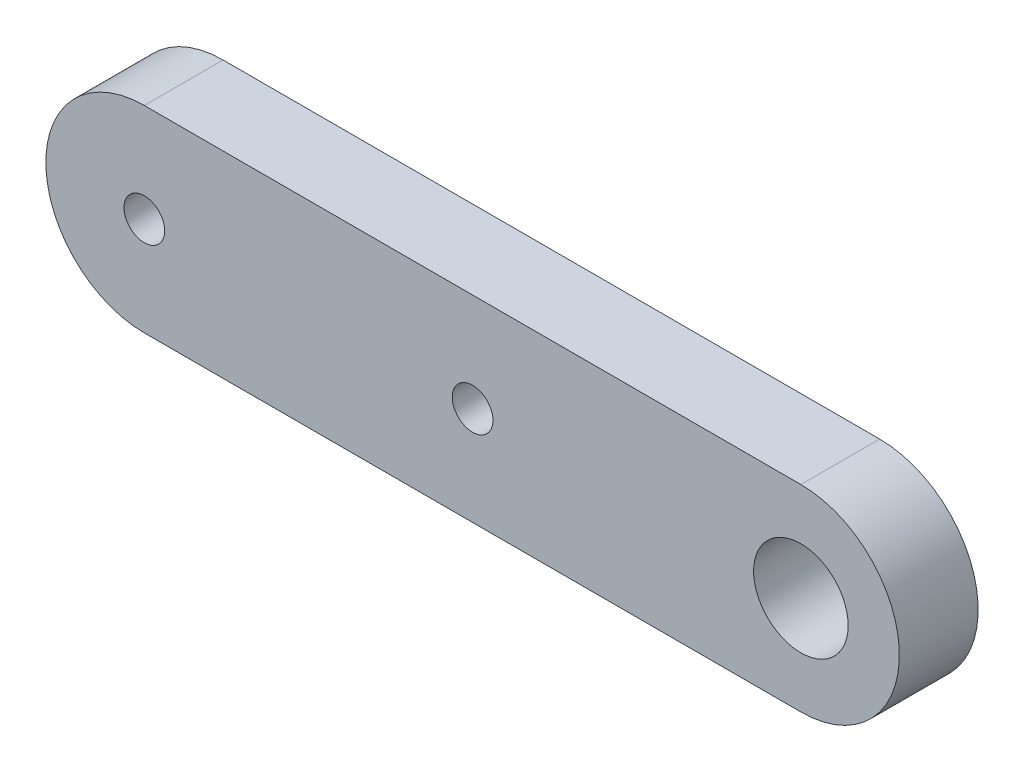
SolidWorks part; units mm, degrees
material "Pine"
ref_plane "Front Plane" through (0, 0, 0) normal (0, 0, 1) x (1, 0, 0)
ref_plane "Top Plane" through (0, 0, 0) normal (0, 1, 0) x (1, 0, 0)
ref_plane "Right Plane" through (0, 0, 0) normal (1, 0, 0) x (0, 0, -1)
sketch "Sketch1" plane through (0, 0, 0) normal (0, 0, 1) x (1, 0, 0)
  line L0 (0, 7.5) -> (50, 7.5)
  line L1 (50, -7.5) -> (0, -7.5)
  circle A0 centre (0, 0) radius 7.5
  circle A1 centre (50, 0) radius 7.5
  dimension "D1" = 50
  dimension "D2" = 15
extrude "Boss-Extrude1" add sketch "Sketch1" along normal blind 6 contours A1 L0 A0 L1 | A1 | A0 region at (25, 0, 0) region at (0, 0, 0) region at (50, 0, 0)
ref_plane "Plane1" through (0, 0, 3) normal (0, 0, 1) x (1, 0, 0)
sketch "Sketch2" plane through (0, 0, 6) normal (0, 0, 1) x (1, 0, 0)
  circle A0 centre (0, 0) radius 1.55
  circle A1 centre (50, 0) radius 1.55
  dimension "D1" = 3.1
extrude "Cut-Extrude1" cut sketch "Sketch2" against normal through all
pattern_linear "LPattern1" count 4 spacing 25 along (1, 0, 0) of "Cut-Extrude1"
sketch "Sketch3" plane through (0, 0, 6) normal (0, 0, 1) x (1, 0, 0)
  circle A0 centre (50, 0) radius 3.6
  dimension "D1" = 7.2
extrude "Cut-Extrude2" cut sketch "Sketch3" against normal through all
